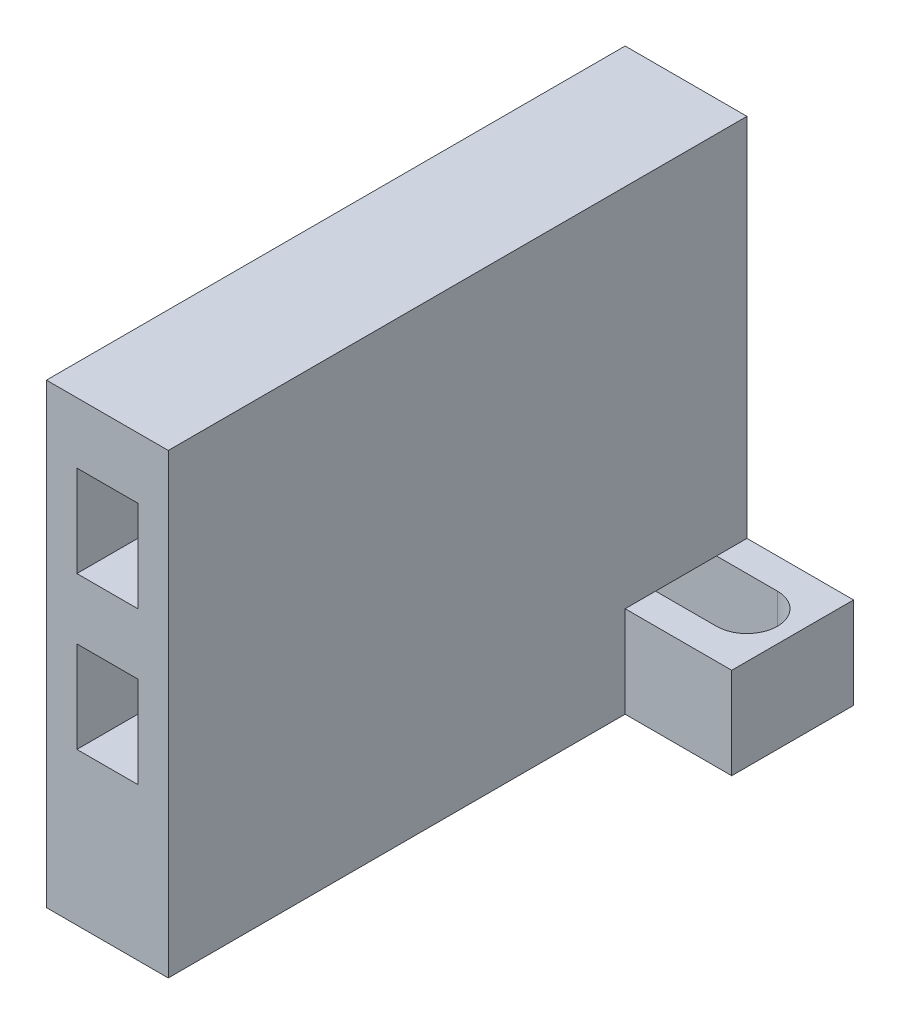
SolidWorks part; units mm, degrees
ref_plane "Спереди" through (0, 0, 0) normal (0, 0, 1) x (1, 0, 0)
ref_plane "Сверху" through (0, 0, 0) normal (0, 1, 0) x (1, 0, 0)
ref_plane "Справа" through (0, 0, 0) normal (1, 0, 0) x (0, 0, -1)
other "Configuration Table"
sketch "Эскиз1" plane through (0, 0, 0) normal (0, 0, 1) x (1, 0, 0)
  line L0 (0, 30) -> (0, 0)
  line L1 (2, 20) -> (6, 20)
  line L2 (2, 20) -> (2, 26)
  line L3 (2, 26) -> (6, 26)
  line L4 (6, 20) -> (6, 26)
  line L5 (2, 16) -> (6, 16)
  line L6 (2, 16) -> (2, 10)
  line L7 (2, 10) -> (6, 10)
  line L8 (6, 16) -> (6, 10)
  line L9 (0, 0) -> (15, 0)
  line L10 (15, 0) -> (15, 6)
  line L11 (15, 6) -> (8, 6)
  line L12 (8, 6) -> (0, 6)
  line L13 (8, 6) -> (8, 30)
  line L14 (8, 30) -> (0, 30)
  line L15 (4, 30) -> (4, -2.8335) construction
  line L16 (8, 6) -> (8, 0)
  dimension "D1" = 4
  dimension "D2" = 8
  dimension "D3" = 4
  dimension "D4" = 4
  dimension "D5" = 6
  dimension "D6" = 4
  dimension "D7" = 15
  dimension "D8" = 6
extrude "Бобышка-Вытянуть1" add sketch "Эскиз1" along normal blind 8 contours L14 L15 L3 L4 L1 L5 L8 L7 L12 L13 | L15 L14 L0 L12 L7 L6 L5 L1 L2 L3 | L12 L15 L9 L10 L11 | L15 L12 L0 L9 | L12 L15 L9 L16 region at (1.6667, 18, 0) region at (2, 3, 0) region at (6.3333, 18, 0) region at (6, 3, 0) region at (11.5, 3, 0)
extrude "Бобышка-Вытянуть2" add sketch "Эскиз1<3>" along normal blind 30 from surface contours L14 L15 L3 L4 L1 L5 L8 L7 L12 L13 | L15 L14 L0 L12 L7 L6 L5 L1 L2 L3 | L15 L12 L0 L9 | L12 L15 L9 L16 region at (1.6667, 18, 0) region at (2, 3, 0) region at (6.3333, 18, 0) region at (6, 3, 0) starting at face at (4, 23, 8)
sketch "Эскиз1<3>" plane through (0, 0, 0) normal (0, 0, 1) x (1, 0, 0) same geometry as "Эскиз1"
sketch "Эскиз2" plane through (0, 0, 0) normal (0, -1, 0) x (1, 0, 0)
  line L0 (15, 4) -> (0, 4) construction
  line L1 (0, 38) -> (0, 0) construction
  line L3 (4, 4) -> (12, 4) construction
  line L4 (4, 6) -> (12, 6)
  line L5 (4, 2) -> (12, 2)
  line L6 (15, 8) -> (15, 0) construction
  line L7 (0, 38) -> (0, 0) construction
  arc A0 (4, 6) -> (4, 2) centre (4, 4) ccw
  arc A1 (12, 2) -> (12, 6) centre (12, 4) ccw
  point P4 (0, 0)
  point P5 (8, 4)
  point P8 (8, 4)
  point P14 (12.2371, 2.8263)
  dimension "D1" = 8
  dimension "D2" = 4
  dimension "D3" = 4
extrude "Вырез-Вытянуть1" cut sketch "Эскиз2" against normal up to surface (6 mm away) contours L5 A1 L4 A0 region at (8, 0, 4) up to face at (11.5, 6, 4)
